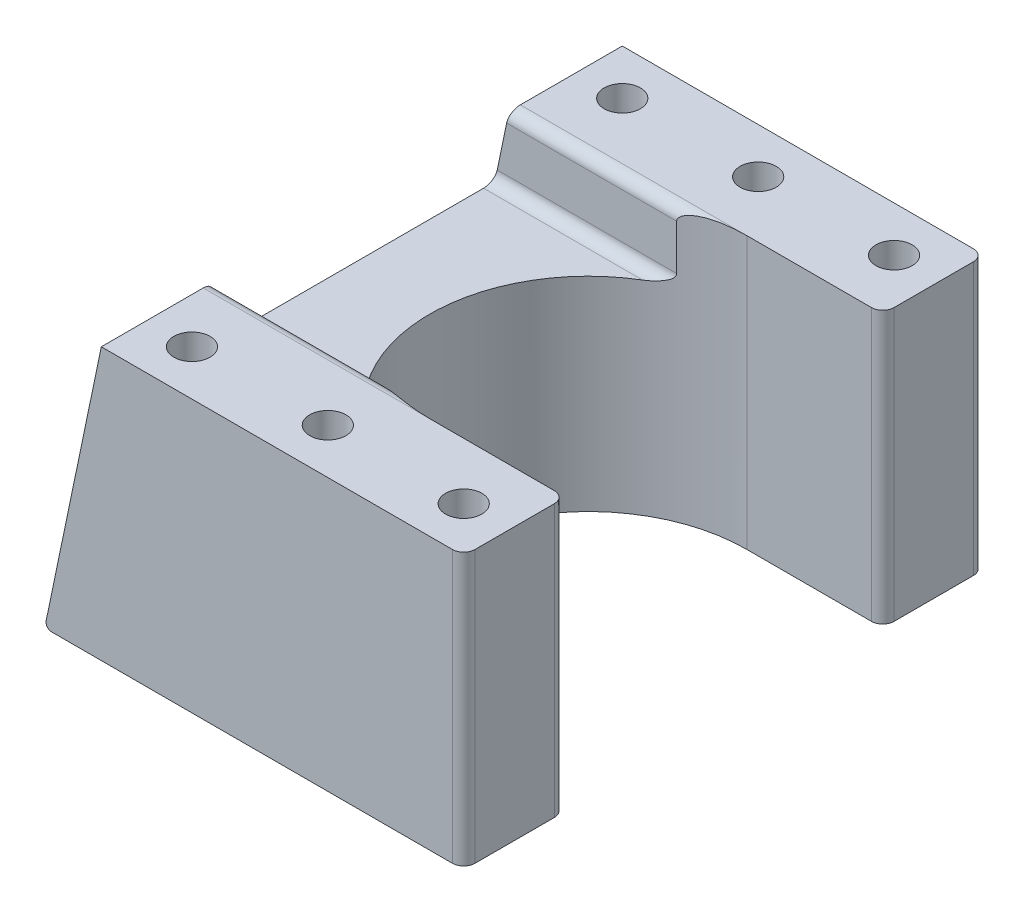
SolidWorks part; units mm, degrees
material "PEI"
ref_plane "Front Plane" through (0, 0, 0) normal (0, 0, 1) x (1, 0, 0)
ref_plane "Top Plane" through (0, 0, 0) normal (0, 1, 0) x (1, 0, 0)
ref_plane "Right Plane" through (0, 0, 0) normal (1, 0, 0) x (0, 0, -1)
sketch "Sketch2" plane through (0, 0, 0) normal (0, 1, 0) x (1, 0, 0)
  line L0 (0, 0) -> (0, 19)
  line L1 (0, 0) -> (-12, 0)
  line L2 (-12, 0) -> (-12, 19)
  line L3 (0, 0) -> (4, 0)
  line L4 (16, -23) -> (-16, -23)
  line L5 (16, -23) -> (16, 23)
  line L6 (16, 23) -> (-16, 23)
  line L7 (-16, -23) -> (-16, 23)
  line L8 (16, -23) -> (-16, 23) construction
  line L9 (16, 23) -> (-16, -23) construction
  line L10 (4, 14) -> (16, 14)
  line L11 (4, -14) -> (16, -14)
  circle A0 centre (-12, 19) radius 1.6
  circle A1 centre (0, 19) radius 1.6
  circle A2 centre (12, 19) radius 1.6
  circle A3 centre (12, -19) radius 1.6
  circle A4 centre (0, -19) radius 1.6
  circle A5 centre (-12, -19) radius 1.6
  circle A6 centre (4, 0) radius 14
  dimension "D3" = 3.2
  dimension "D4" = 3.2
  dimension "D7" = 28
  dimension "D1" = 12
  dimension "D2" = 19
  dimension "D5" = 19
  dimension "D6" = 4
  dimension "D8" = 46
  dimension "D9" = 32
extrude "Boss-Extrude1" add sketch "Sketch2" along normal blind 24 contours A6 L5 L6 L7 L4 A0 A1 A4 A3 A2 A5 region at (-7.6743, 0, -8.7015)
sketch "Sketch4" plane through (0, 0, 23) normal (0, 0, 1) x (1, 0, 0)
  line L0 (-16, 0) -> (-21, 0)
  line L1 (-21, 0) -> (-16, 24)
  line L4 (-16, 0) -> (16, 0)
  line L5 (16, 0) -> (16, 24)
  line L6 (16, 24) -> (-16, 24)
  line L7 (-16, 24) -> (-16, 0)
  line L8 (-16, 0) -> (16, 0)
  line L9 (16, 0) -> (16, 24)
  line L10 (16, 24) -> (-16, 24)
  line L11 (-16, 24) -> (-16, 0)
  line M9 (-16, 24) -> (-16, 0)
  dimension "D2" = 5
  dimension "D1" = 0
extrude "Boss-Extrude2" add sketch "Sketch4" against normal up to surface (46 mm away) contours L1 L0 M9 region at (-17.6667, 8, 23) up to face at (0, 12, -23)
sketch "Sketch5" plane through (0, 24, 0) normal (0, 1, 0) x (1, 0, 0)
  line L0 (0, 0) -> (-21, 0)
  line L1 (0, 13) -> (-21, 13)
  line L2 (0, -13) -> (-21, -13)
  line L4 (-16, -23) -> (-16, 23)
  line L5 (-16, 23) -> (-21, 23)
  line L6 (-21, 23) -> (-21, -23)
  line L7 (-21, -23) -> (-16, -23)
  line L8 (-16, -23) -> (-16, 23)
  line L9 (-16, 23) -> (-21, 23)
  line L10 (-21, 23) -> (-21, -23)
  line L11 (-21, -23) -> (-16, -23)
  line L15 (4, 14) -> (16, 14)
  line L16 (16, 14) -> (16, 23)
  line L17 (16, 23) -> (-16, 23)
  line L18 (-16, 23) -> (-16, -23)
  line L19 (-16, -23) -> (16, -23)
  line L20 (16, -23) -> (16, -14)
  line L21 (16, -14) -> (4, -14)
  line L22 (4, 14) -> (16, 14)
  line L23 (16, 14) -> (16, 23)
  line L24 (16, 23) -> (-16, 23)
  line L25 (-16, 23) -> (-16, -23)
  line L26 (-16, -23) -> (16, -23)
  line L27 (16, -23) -> (16, -14)
  line L28 (16, -14) -> (4, -14)
  arc A1 (4, 14) -> (4, -14) centre (4, 0) ccw
  arc A2 (4, 14) -> (4, -14) centre (4, 0) ccw
  arc M16 (4, -14) -> (4, 14) centre (4, 0) cw
  line M20 (-16, 23) -> (-16, -23)
  dimension "D1" = 0
  dimension "D2" = 0
  dimension "D3" = 13
  dimension "D4" = 13
extrude "Cut-Extrude1" cut sketch "Sketch5" against normal blind 6 contours L1 L0 M16 M20 | L1 L10 L0 M20 | L2 L0 M16 M20 | L0 L10 L2 M20 region at (-11.4463, 24, 7.5042) region at (-11.4463, 24, -7.5042) region at (-18.5, 24, 6.5) region at (-18.5, 24, -6.5)
fillet "Fillet1" radius 1 4 edges at (-9.2231, 18, 13) (-9.2231, 18, -13) (-8.5981, 24, 13) (-8.5981, 24, -13)
fillet "Fillet2" radius 0.5 1 edges at (-21, 0, 0)
fillet "Fillet3" radius 1 4 edges at (16, 12, -23) (16, 12, -14) (16, 12, 14) (16, 12, 23)
